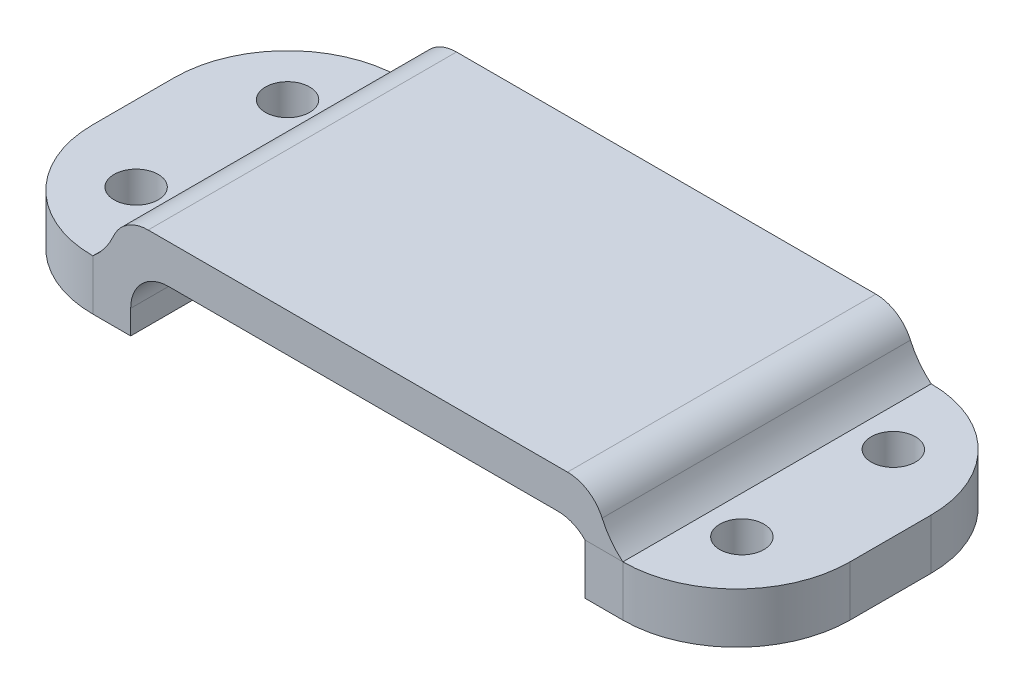
SolidWorks part; units mm, degrees
ref_plane "Front Plane" through (0, 0, 0) normal (0, 0, 1) x (1, 0, 0)
ref_plane "Top Plane" through (0, 0, 0) normal (0, 1, 0) x (1, 0, 0)
ref_plane "Right Plane" through (0, 0, 0) normal (1, 0, 0) x (0, 0, -1)
sketch "Sketch2" plane through (0, 0, 0) normal (0, 1, 0) x (1, 0, 0)
  line L0 (-18, 12.215) -> (-30, 12.215)
  line L1 (30, -12.215) -> (18, -12.215)
  line L2 (30, -12.215) -> (30, 12.215)
  line L3 (30, 12.215) -> (18, 12.215)
  line L4 (-30, -12.215) -> (-30, 12.215)
  line L5 (30, -12.215) -> (18, -7.329) construction
  line L6 (30, 12.215) -> (18, 7.329) construction
  line L7 (-30, 12.215) -> (-18, 12.215)
  line L8 (-30, 12.215) -> (-30, -12.215)
  line L9 (-30, -12.215) -> (-18, -12.215)
  line L10 (-18, 12.215) -> (-18, -12.215)
  line L11 (30, 12.215) -> (18, 12.215)
  line L12 (30, 12.215) -> (30, -12.215)
  line L13 (30, -12.215) -> (18, -12.215)
  line L14 (18, 12.215) -> (18, -12.215)
  line L15 (0, 0) -> (-30, -12.215) construction
  line L16 (0, 0) -> (-30, 12.215) construction
  line L17 (-18, -12.215) -> (-30, -12.215)
  point P0 (0, 0)
extrude "Boss-Extrude1" add sketch "Sketch2" along normal blind 4 contours L10 L0 L4 L9 | L3 L14 L1 L2 region at (-24, 0, 0) region at (24, 0, 0)
sketch "Sketch3" plane through (0, 4, 0) normal (0, 1, 0) x (1, 0, 0)
  line L0 (-18, 12.215) -> (-30, 12.215) construction
  circle A0 centre (-24, 6.215) radius 1.75
  circle A1 centre (24, 6.215) radius 1.75
  circle A2 centre (24, -5.785) radius 1.75
  circle A3 centre (-24, -5.785) radius 1.75
  dimension "D1" = 6
  dimension "D4" = 3.5
  dimension "D2" = 2
  dimension "D3" = 2
extrude "Cut-Extrude1" cut sketch "Sketch3" against normal blind 4
fillet "Fillet1" radius 9 2 edges at (-30, 2, 12.215) (-30, 2, -12.215)
fillet "Fillet2" radius 9 2 edges at (30, 2, -12.215) (30, 2, 12.215)
sketch "Sketch4" plane through (0, 0, 0) normal (0, 0, 1) x (1, 0, 0)
  line L5 (-21, 4) -> (-19.6147, 4.9)
  line L6 (-18, 4) -> (-21, 4)
  line L7 (-18, 4) -> (-18, 4.9)
  line L8 (-18, 4.9) -> (-19.6147, 4.9)
  line L11 (-18, 4.9) -> (-19.6147, 4.9)
  line L12 (-18, 4.9) -> (-18, 7.9654)
  line L13 (-18, 7.9654) -> (-19.6147, 7.9654)
  line L14 (-19.6147, 4.9) -> (-19.6147, 7.9654)
  line L15 (-18, 7.9654) -> (0, 7.9654)
  line L16 (-18, 7.9654) -> (-18, 4.9)
  line L17 (-18, 4.9) -> (0, 4.9)
  line L18 (0, 7.9654) -> (0, 4.9)
extrude "Boss-Extrude2" add sketch "Sketch4" along normal up to surface and the other way up to surface contours L18 L15 L12 L17 | L14 L8 L12 L13 | L7 L8 L5 L6 region at (-19.1883, 4.405, 0) region at (-18.8073, 6.4327, 0) region at (-9, 6.4327, 0) up to face at (-19.5, 2, 12.215) other way up to face at (-19.5, 2, -12.215)
mirror "Mirror1" about plane through (0, 0, 0) normal (1, 0, 0) of "Boss-Extrude2"
fillet "Fillet3" radius 3 4 edges at (19.6147, 7.9654, 0) (-19.6147, 7.9654, 0) (18, 4.9, 0) (-18, 4.9, 0)
fillet "Fillet4" radius 6 2 edges at (19.6147, 4.9, 0) (-19.6147, 4.9, 0)
